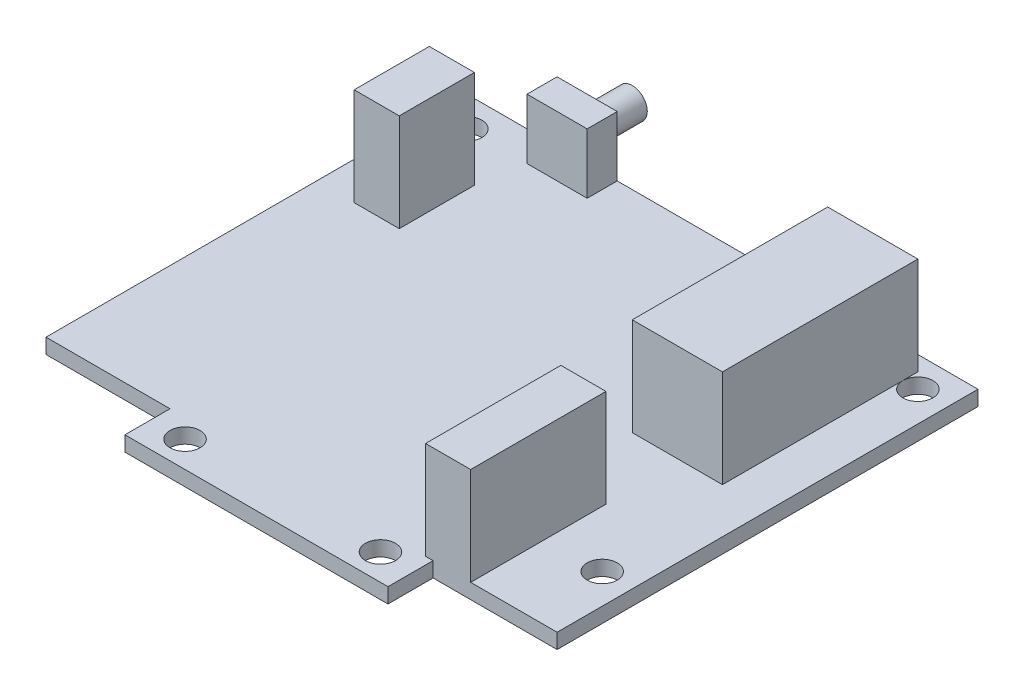
SolidWorks part; units mm, degrees
ref_plane "Front Plane" through (0, 0, 0) normal (0, 0, 1) x (1, 0, 0)
ref_plane "Top Plane" through (0, 0, 0) normal (0, 1, 0) x (1, 0, 0)
ref_plane "Right Plane" through (0, 0, 0) normal (1, 0, 0) x (0, 0, -1)
sketch "Sketch1" plane through (0, 0, 0) normal (0, 1, 0) x (1, 0, 0)
  line L0 (13.8906, -22.225) -> (26.9875, -22.225)
  line L1 (-26.9875, 22.225) -> (26.9875, 22.225)
  line L2 (-26.9875, 22.225) -> (-26.9875, -22.225)
  line L3 (-26.9875, -22.225) -> (-13.8906, -22.225)
  line L4 (26.9875, 22.225) -> (26.9875, -22.225)
  line L5 (-26.9875, 22.225) -> (26.9875, -22.225) construction
  line L6 (-26.9875, -22.225) -> (26.9875, 22.225) construction
  line L8 (-13.8906, -22.225) -> (-13.8906, -26.9875)
  line L9 (-13.8906, -26.9875) -> (13.8906, -26.9875)
  line L10 (13.8906, -22.225) -> (13.8906, -26.9875)
  point P0 (0, 0)
  point P10 (0, -26.9875)
  dimension "D1" = 53.975
  dimension "D2" = 44.45
  dimension "D3" = 27.7812
  dimension "D4" = 4.7625
extrude "Boss-Extrude1" add sketch "Sketch1" along normal blind 1.5875
sketch "Sketch2" plane through (0, 1.5875, 0) normal (0, 1, 0) x (1, 0, 0)
  line L0 (13.8906, -22.225) -> (26.9875, -22.225) construction
  line L1 (13.0969, -22.225) -> (17.8594, -22.225)
  line L2 (13.0969, -22.225) -> (13.0969, -7.9375)
  line L3 (13.0969, -7.9375) -> (17.8594, -7.9375)
  line L4 (17.8594, -22.225) -> (17.8594, -7.9375)
  line L5 (13.8906, -26.9875) -> (13.8906, -22.225) construction
  line L6 (-26.9875, 22.225) -> (-26.9875, -22.225) construction
  line L7 (-23.0188, 14.2875) -> (-18.2563, 14.2875)
  line L8 (-23.0188, 14.2875) -> (-23.0188, 6.35)
  line L9 (-23.0188, 6.35) -> (-18.2563, 6.35)
  line L10 (-18.2563, 14.2875) -> (-18.2563, 6.35)
  line L11 (26.9875, 22.225) -> (-26.9875, 22.225) construction
  line L12 (26.9875, -22.225) -> (26.9875, 22.225) construction
  line L13 (-17.4625, 22.225) -> (-11.1125, 22.225)
  line L14 (-17.4625, 22.225) -> (-17.4625, 19.05)
  line L15 (-17.4625, 19.05) -> (-11.1125, 19.05)
  line L16 (-11.1125, 22.225) -> (-11.1125, 19.05)
  line L17 (12.7, 20.6375) -> (22.225, 20.6375)
  line L18 (12.7, 20.6375) -> (12.7, 0)
  line L19 (12.7, 0) -> (22.225, 0)
  line L20 (22.225, 20.6375) -> (22.225, 0)
  line M18 (26.9875, 22.225) -> (-26.9875, 22.225)
  line M24 (13.8906, -22.225) -> (26.9875, -22.225)
  dimension "D1" = 14.2875
  dimension "D2" = 4.7625
  dimension "D3" = 0.7937
  dimension "D4" = 3.9688
  dimension "D5" = 4.7625
  dimension "D6" = 7.9375
  dimension "D7" = 7.9375
  dimension "D8" = 9.525
  dimension "D9" = 6.35
  dimension "D10" = 3.175
  dimension "D11" = 9.525
  dimension "D12" = 20.6375
  dimension "D13" = 1.5875
  dimension "D14" = 4.7625
extrude "Boss-Extrude2" add sketch "Sketch2" along normal blind 10.3187 separate body contours L10 L7 L8 L9 | L16 L14 L15 M18 region at (-20.6375, 1.5875, -10.3188) region at (-14.2875, 1.5875, -20.6375)
extrude "Boss-Extrude7" add sketch "Sketch2<3>" along normal up to surface (10.3187 mm away) contours L20 L17 L18 L19 region at (17.4625, 1.5875, -10.3188) up to face at (-20.6375, 11.9062, -10.3188)
sketch "Sketch2<3>" plane through (0, 1.5875, 0) normal (0, 1, 0) x (1, 0, 0) same geometry as "Sketch2"
extrude "Boss-Extrude8" add sketch "Sketch2<4>" along normal up to surface (10.3187 mm away) contours L4 L3 L2 L1 M24 region at (15.4781, 1.5875, 15.0812) up to face at (-14.2875, 11.9062, -20.6375)
sketch "Sketch2<4>" plane through (0, 1.5875, 0) normal (0, 1, 0) x (1, 0, 0) same geometry as "Sketch2"
sketch "Sketch3" plane through (0, 0, -22.225) normal (0, 0, -1) x (-1, 0, 0)
  line L1 (11.1125, 11.9062) -> (11.1125, 1.5875) construction
  line L2 (17.4625, 1.5875) -> (11.1125, 1.5875) construction
  line L3 (17.4625, 1.5875) -> (17.4625, 7.9375) construction
  line L4 (17.4625, 7.9375) -> (11.1125, 7.9375) construction
  line L5 (11.1125, 1.5875) -> (11.1125, 7.9375) construction
  line L6 (-26.9875, 1.5875) -> (26.9875, 1.5875) construction
  line L7 (17.4625, 11.9062) -> (17.4625, 1.5875) construction
  line L8 (11.1125, 11.9062) -> (17.4625, 11.9062) construction
  circle A0 centre (14.2875, 4.7625) radius 1.5875
  point P4 (14.2875, 11.9062)
  point P14 (17.4625, 4.7625)
  dimension "D2" = 3.175
  dimension "D1" = 6.35
extrude "Boss-Extrude3" add sketch "Sketch3" along normal blind 4.7625
sketch "Sketch4" plane through (0, 0, -22.225) normal (0, 0, -1) x (-1, 0, 0)
  line L0 (11.1125, 11.9062) -> (11.1125, 1.5875) construction
  line L1 (17.4625, 11.9062) -> (11.1125, 11.9062)
  line L2 (17.4625, 11.9062) -> (17.4625, 7.9375)
  line L3 (17.4625, 7.9375) -> (11.1125, 7.9375)
  line L4 (11.1125, 11.9062) -> (11.1125, 7.9375)
  line L5 (-26.9875, 1.5875) -> (26.9875, 1.5875) construction
  dimension "D1" = 6.35
extrude "Cut-Extrude1" cut sketch "Sketch4" against normal through all
sketch "Sketch5" plane through (0, 0, 0) normal (0, -1, 0) x (1, 0, 0)
  line L0 (26.9875, -22.225) -> (-26.9875, -22.225) construction
  line L1 (8.7312, -20.6375) -> (-8.7312, -20.6375)
  line L2 (8.7312, -20.6375) -> (8.7313, -13.8906)
  line L3 (8.7312, -3.175) -> (-8.7312, -3.175)
  line L4 (-8.7312, -20.6375) -> (-8.7313, -13.8906)
  line L5 (-8.7313, -13.8906) -> (-10.3188, -13.8906)
  line L6 (-8.7313, -9.9219) -> (-10.3188, -9.9219)
  line L7 (0, -20.6375) -> (0, -3.175) construction
  line L8 (-8.7313, -9.9219) -> (-8.7312, -3.175)
  line L9 (8.7313, -9.9219) -> (10.3188, -9.9219)
  line L10 (8.7313, -13.8906) -> (10.3188, -13.8906)
  line L11 (8.7313, -9.9219) -> (8.7312, -3.175)
  arc A0 (-10.3188, -13.8906) -> (-10.3188, -9.9219) centre (-10.3188, -11.9063) cw
  arc A1 (10.3188, -13.8906) -> (10.3188, -9.9219) centre (10.3188, -11.9063) ccw
  point P5 (0, -3.175)
  point P17 (0, -11.9063)
  dimension "D4" = 1.9844
  dimension "D1" = 17.4625
  dimension "D2" = 1.5875
  dimension "D3" = 1.5875
  dimension "D5" = 17.4625
extrude "Boss-Extrude4" add sketch "Sketch5" along normal blind 7.9375
sketch "Sketch6" plane through (0, -7.9375, 0) normal (0, -1, 0) x (1, 0, 0)
  line L0 (-8.7312, -20.6375) -> (8.7312, -20.6375) construction
  line L2 (1.1906, -20.6375) -> (-1.1906, -20.6375)
  line L3 (1.1906, -20.6375) -> (1.1906, -19.7539)
  line L5 (-1.1906, -20.6375) -> (-1.1906, -19.7539)
  arc A0 (1.1906, -19.7539) -> (-1.1906, -19.7539) centre (0, -11.9063) ccw
  arc A1 (10.3188, -13.8906) -> (10.3188, -9.9219) centre (10.3188, -11.9063) ccw construction
  point P6 (12.3031, -11.9063)
  point P10 (0, -20.6375)
  point P15 (0, -20.6375)
  dimension "D1" = 15.875
  dimension "D2" = 2.3813
extrude "Boss-Extrude5" add sketch "Sketch6" along normal blind 6.35
sketch "Sketch7" plane through (0, 0, 0) normal (0, -1, 0) x (1, 0, 0)
  line L0 (-26.9875, -22.225) -> (-26.9875, 22.225) construction
  line L1 (26.9875, 22.225) -> (26.9875, -22.225) construction
  line L2 (26.9875, -22.225) -> (-26.9875, -22.225) construction
  line L3 (13.8906, 22.225) -> (26.9875, 22.225) construction
  line L4 (13.8906, 26.9875) -> (13.8906, 22.225) construction
  line L5 (-13.8906, 22.225) -> (-13.8906, 26.9875) construction
  line L6 (-13.8906, 26.9875) -> (13.8906, 26.9875) construction
  circle A0 centre (23.8125, -19.05) radius 1.5875
  circle A2 centre (-23.8125, -19.05) radius 1.5875
  circle A3 centre (-10.3187, 24.2094) radius 1.5875
  circle A4 centre (10.3187, 24.2094) radius 1.5875
  circle A5 centre (23.8125, 14.2875) radius 1.5875
  dimension "D8" = 3.175
  dimension "D1" = 3.175
  dimension "D2" = 3.175
  dimension "D3" = 3.175
  dimension "D4" = 7.9375
  dimension "D5" = 3.5719
  dimension "D6" = 3.5719
  dimension "D7" = 2.7781
extrude "Cut-Extrude2" cut sketch "Sketch7" against normal through all
sketch "Sketch8" plane through (0, 1.5875, 0) normal (0, 1, 0) x (1, 0, 0)
  line L0 (-26.9875, -2.6827) -> (26.9875, -2.6827) construction
  line L1 (-26.9875, 22.225) -> (-26.9875, -22.225) construction
  line L2 (26.9875, -22.225) -> (26.9875, 22.225) construction
  text T0 "Pixy"
sketch "Sketch9" plane through (0, 0, 0) normal (0, -1, 0) x (1, 0, 0)
  line L0 (-13.8906, 26.9875) -> (13.8906, 26.9875) construction
  line L1 (1.5875, 22.225) -> (-1.5875, 22.225)
  line L2 (1.5875, 22.225) -> (1.5875, 24.6062)
  line L3 (1.5875, 24.6062) -> (-1.5875, 24.6062)
  line L4 (-1.5875, 22.225) -> (-1.5875, 24.6062)
  line L5 (13.8906, 22.225) -> (26.9875, 22.225) construction
  point P6 (0, 24.6062)
  point P7 (0, 26.9875)
  dimension "D1" = 3.175
  dimension "D2" = 2.3813
extrude "Boss-Extrude6" add sketch "Sketch9" along normal blind 1.5875
